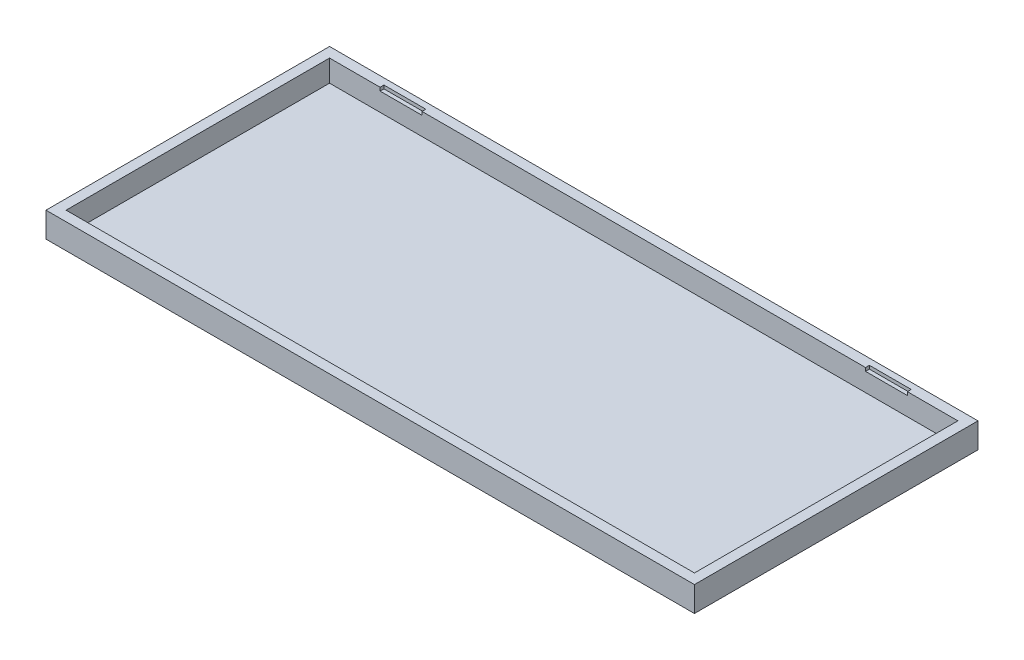
SolidWorks part; units mm, degrees
ref_plane "Front Plane" through (0, 0, 0) normal (0, 0, 1) x (1, 0, 0)
ref_plane "Top Plane" through (0, 0, 0) normal (0, 1, 0) x (1, 0, 0)
ref_plane "Right Plane" through (0, 0, 0) normal (1, 0, 0) x (0, 0, -1)
sketch "Sketch1" plane through (0, 0, 0) normal (0, 1, 0) x (1, 0, 0)
  line L1 (-193.7, 84.7) -> (193.7, 84.7)
  line L2 (-193.7, 84.7) -> (-193.7, -84.7)
  line L3 (-193.7, -84.7) -> (193.7, -84.7)
  line L4 (193.7, 84.7) -> (193.7, -84.7)
  line L5 (-193.7, 84.7) -> (193.7, -84.7) construction
  line L6 (-193.7, -84.7) -> (193.7, 84.7) construction
  point P0 (0, 0)
  dimension "D1" = 387.4
  dimension "D2" = 169.4
extrude "Boss-Extrude1" add sketch "Sketch1" along normal blind 15
sketch "Sketch2" plane through (0, 15, 0) normal (0, 1, 0) x (1, 0, 0)
  line L0 (0, 78.7) -> (0, 84.7) construction
  line L2 (-187.7, 78.7) -> (187.7, 78.7)
  line L3 (-187.7, 78.7) -> (-187.7, -78.7)
  line L4 (-187.7, -78.7) -> (187.7, -78.7)
  line L5 (187.7, 78.7) -> (187.7, -78.7)
  line L6 (-187.7, 78.7) -> (187.7, -78.7) construction
  line L7 (-187.7, -78.7) -> (187.7, 78.7) construction
  line L8 (193.7, 84.7) -> (-193.7, 84.7) construction
  line L9 (187.7, 0) -> (193.7, 0) construction
  line L10 (193.7, -84.7) -> (193.7, 84.7) construction
  point P0 (0, 0)
  dimension "D1" = 6
  dimension "D2" = 6
extrude "Cut-Extrude1" cut sketch "Sketch2" against normal offset from surface (13 mm away) 2 up to face at (0, 0, 0)
sketch "Sketch3" plane through (0, 15, 0) normal (0, 1, 0) x (1, 0, 0)
  line L0 (193.7, 84.7) -> (157.5, 84.7) construction
  line L1 (193.7, 84.7) -> (-193.7, 84.7) construction
  line L2 (157.5, 81) -> (157.5, 78.7)
  line L3 (-187.7, 78.7) -> (187.7, 78.7) construction
  line L4 (157.5, 78.7) -> (132.5, 78.7)
  line L5 (187.7, 78.7) -> (-187.7, 78.7) construction
  line L6 (132.5, 78.7) -> (132.5, 81)
  line L7 (132.5, 81) -> (157.5, 81)
  line L8 (157.5, 81) -> (157.5, 84.7) construction
  line L9 (-193.7, 84.7) -> (-157.5, 84.7) construction
  line L10 (-157.5, 81) -> (-157.5, 78.7)
  line L11 (-157.5, 78.7) -> (-132.5, 78.7)
  line L12 (-132.5, 78.7) -> (-132.5, 81)
  line L13 (-132.5, 81) -> (-157.5, 81)
  line L14 (-157.5, 81) -> (-157.5, 84.7) construction
  dimension "D1" = 36.2
  dimension "D2" = 2.3
  dimension "D3" = 25
  dimension "D4" = 36.2
  dimension "D5" = 2.3
  dimension "D6" = 25
extrude "Cut-Extrude2" cut sketch "Sketch3" against normal blind 2
equation "\"full_width\"=375"
equation "\"D1@Sketch1\"=\"full_width\"+(\"added_width\"*2)+(\"margin1\"*2)"
equation "\"added_width\"=6"
equation "\"full_height\"= 157"
equation "\"D2@Sketch1\"=\"full_height\"+(\"added_height\"*2)+(\"margin1\"*2)"
equation "\"added_height\"=6"
equation "\"D1@Sketch3\"=30.00mm+\"added_width\"+\"margin1\""
equation "\"tab_depth\"=2.5"
equation "\"D2@Sketch3\"=\"tab_depth\"-\"margin1\""
equation "\"tab_width\"=25"
equation "\"D3@Sketch3\"=\"tab_width\""
equation "\"tab_height\"=2"
equation "\"D1@Cut-Extrude2\"=\"tab_height\""
equation "\"D4@Sketch3\"=30mm+\"added_width\"+\"margin1\""
equation "\"D5@Sketch3\"=\"tab_depth\"-\"margin1\""
equation "\"D6@Sketch3\"=\"tab_width\""
equation "\"D2@Sketch2\"=\"added_height\""
equation "\"D1@Sketch2\"=\"added_width\""
equation "\"margin1\"= 0.2"
